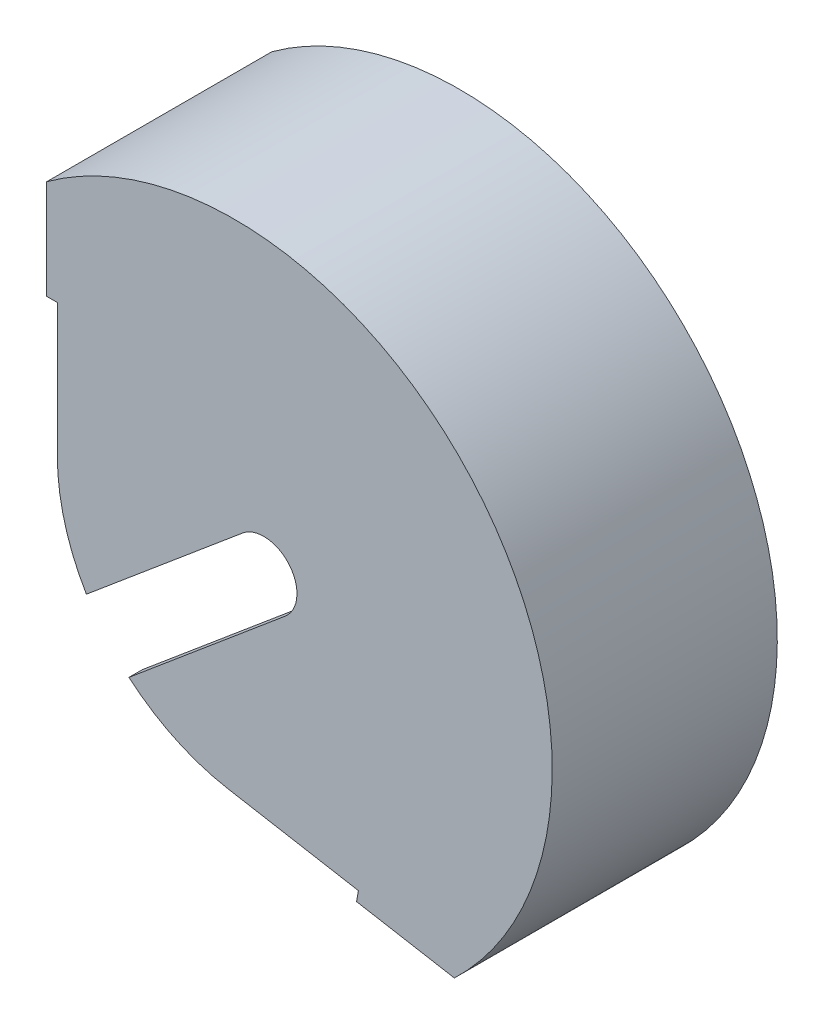
SolidWorks part; units mm, degrees
ref_plane "Front Plane" through (0, 0, 0) normal (0, 0, 1) x (1, 0, 0)
ref_plane "Top Plane" through (0, 0, 0) normal (0, 1, 0) x (1, 0, 0)
ref_plane "Right Plane" through (0, 0, 0) normal (1, 0, 0) x (0, 0, -1)
sketch "Sketch1" plane through (0, 0, 0) normal (0, 0, 1) x (1, 0, 0)
  line L0 (0, 0) -> (-39.624, 0)
  line L1 (0, 0) -> (-6.8806, -39.022)
  line L2 (-39.624, 0) -> (-39.624, 25.4)
  line L3 (-6.8806, -39.022) -> (18.1335, -43.4327)
  line L4 (-39.624, 25.4) -> (-41.656, 25.4)
  line L5 (18.1335, -43.4327) -> (17.7806, -45.4338)
  line L6 (-41.656, 25.4) -> (-41.656, 44.45)
  line L7 (17.7806, -45.4338) -> (36.5412, -48.7418)
  arc A0 (-39.624, 0) -> (-6.8806, -39.022) centre (0, 0) ccw
  arc A1 (36.5412, -48.7418) -> (-41.656, 44.45) centre (-5.6446, -4.7364) ccw
  dimension "D1" = 79.248
  dimension "D8" = 60.96
  dimension "D2" = 80
  dimension "D3" = 25.4
  dimension "D4" = 25.4
  dimension "D5" = 2.032
  dimension "D6" = 2.032
  dimension "D7" = 19.05
extrude "Boss-Extrude1" add sketch "Sketch1" along normal blind 2.54 contours L7 A1 L6 L4 L2 L0 L1 L3 L5 | L0 A0 L1 region at (-18.6316, -15.6338, 0) region at (10.1938, 8.5536, 0)
sketch "Sketch2" plane through (0, 0, 2.54) normal (0, 0, 1) x (1, 0, 0)
  line L0 (-40.1555, 42.4006) -> (-41.656, 42.4006)
  line L2 (34.7835, -46.9083) -> (34.5229, -48.3859)
  line L4 (-41.656, 25.4) -> (-41.656, 44.45) construction
  line L5 (17.7806, -45.4338) -> (36.5412, -48.7418) construction
  line L6 (-41.656, 42.4006) -> (-41.656, 44.45)
  line L7 (34.5229, -48.3859) -> (36.5412, -48.7418)
  arc A2 (34.7835, -46.9083) -> (-40.1555, 42.4006) centre (-5.6446, -4.7364) ccw
  arc A3 (34.7835, -46.9083) -> (-40.1555, 42.4006) centre (-5.6446, -4.7364) ccw
  arc A5 (36.5412, -48.7418) -> (-41.656, 44.45) centre (-5.6446, -4.7364) ccw
  arc A6 (36.5412, -48.7418) -> (-41.656, 44.45) centre (-5.6446, -4.7364) ccw
  line M6 (18.1335, -43.4327) -> (17.7806, -45.4338)
  line M7 (17.7806, -45.4338) -> (36.5412, -48.7418)
  arc M8 (36.5412, -48.7418) -> (-41.656, 44.45) centre (-5.6446, -4.7364) ccw
  line M9 (-41.656, 44.45) -> (-41.656, 25.4)
  line M10 (-41.656, 25.4) -> (-39.624, 25.4)
  dimension "D1" = 2.54
  dimension "D2" = 0
extrude "Boss-Extrude2" add sketch "Sketch2" along normal blind 38.1 contours A3 L2 L0 M6 M7 M8 M9 M10 region at (-40.9058, 43.8296, 2.54)
ref_plane "midplane" through (0, 0, 21.59) normal (0, 0, 1) x (1, 0, 0)
mirror "Mirror1" about plane through (0, 0, 21.59) normal (0, 0, 1) of "Boss-Extrude1"
sketch "Sketch3" plane through (0, 0, 43.18) normal (0, 0, 1) x (1, 0, 0)
  line L0 (0, 0) -> (-30.3537, -25.4698) construction
  line L1 (-4.0817, 4.8644) -> (-37.1595, -22.8912)
  line L2 (-37.1595, -22.8912) -> (-28.9961, -32.62)
  line L3 (-28.9961, -32.62) -> (4.0817, -4.8644)
  arc A0 (4.0817, -4.8644) -> (-4.0817, 4.8644) centre (0, 0) ccw
  arc A1 (-39.624, 0) -> (-6.8806, -39.022) centre (0, 0) ccw construction
  dimension "D2" = 12.7
  dimension "D1" = 43.18
extrude "Cut-Extrude1" cut sketch "Sketch3" against normal up to next
